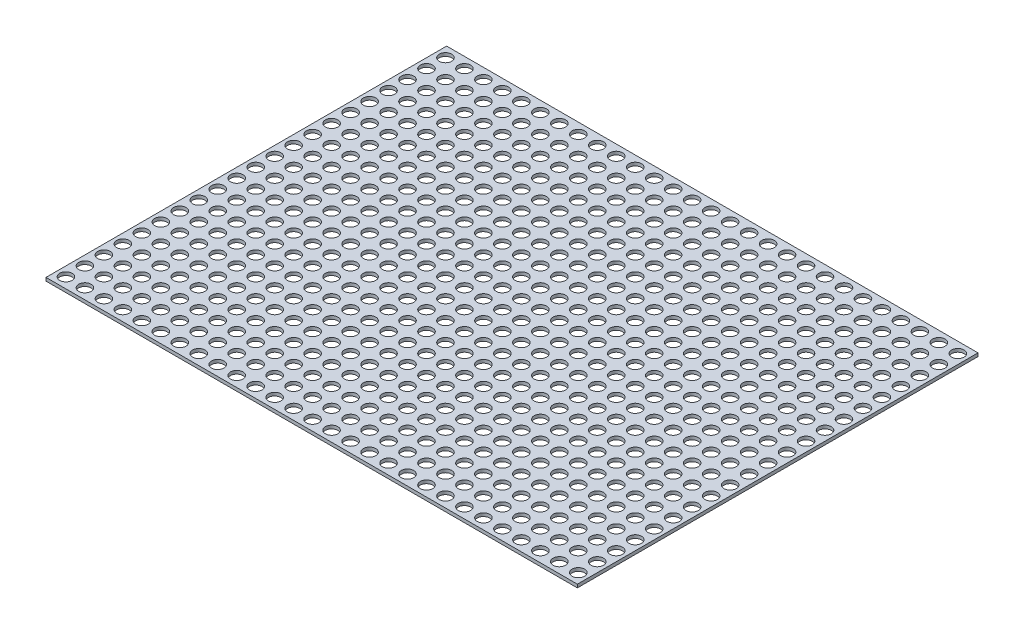
SolidWorks part; units mm, degrees
ref_plane "Front Plane" through (0, 0, 0) normal (0, 0, 1) x (1, 0, 0)
ref_plane "Top Plane" through (0, 0, 0) normal (0, 1, 0) x (1, 0, 0)
ref_plane "Right Plane" through (0, 0, 0) normal (1, 0, 0) x (0, 0, -1)
sketch "Sketch1" plane through (0, 0, 0) normal (0, 1, 0) x (1, 0, 0)
  line L0 (4.5, 4.95) -> (13.5, 4.95) construction
  line L1 (0, 0) -> (252, 0)
  line L2 (0, 0) -> (0, 190)
  line L3 (0, 190) -> (252, 190)
  line L4 (252, 0) -> (252, 190)
  line L5 (4.5, 4.95) -> (4.5, 13.95) construction
  circle A0 centre (4.5, 4.95) radius 2.95
  circle A1 centre (13.5, 4.95) radius 2.95
  circle A2 centre (22.5, 4.95) radius 2.95
  circle A3 centre (31.5, 4.95) radius 2.95
  circle A4 centre (40.5, 4.95) radius 2.95
  circle A5 centre (49.5, 4.95) radius 2.95
  circle A6 centre (58.5, 4.95) radius 2.95
  circle A7 centre (67.5, 4.95) radius 2.95
  circle A8 centre (76.5, 4.95) radius 2.95
  circle A9 centre (85.5, 4.95) radius 2.95
  circle A10 centre (94.5, 4.95) radius 2.95
  circle A11 centre (103.5, 4.95) radius 2.95
  circle A12 centre (112.5, 4.95) radius 2.95
  circle A13 centre (121.5, 4.95) radius 2.95
  circle A14 centre (130.5, 4.95) radius 2.95
  circle A15 centre (139.5, 4.95) radius 2.95
  circle A16 centre (148.5, 4.95) radius 2.95
  circle A17 centre (157.5, 4.95) radius 2.95
  circle A18 centre (166.5, 4.95) radius 2.95
  circle A19 centre (175.5, 4.95) radius 2.95
  circle A20 centre (184.5, 4.95) radius 2.95
  circle A21 centre (193.5, 4.95) radius 2.95
  circle A22 centre (202.5, 4.95) radius 2.95
  circle A23 centre (211.5, 4.95) radius 2.95
  circle A24 centre (220.5, 4.95) radius 2.95
  circle A25 centre (229.5, 4.95) radius 2.95
  circle A26 centre (238.5, 4.95) radius 2.95
  circle A27 centre (247.5, 4.95) radius 2.95
  circle A28 centre (13.5, 13.95) radius 2.95
  circle A29 centre (22.5, 13.95) radius 2.95
  circle A30 centre (31.5, 13.95) radius 2.95
  circle A31 centre (40.5, 13.95) radius 2.95
  circle A32 centre (49.5, 13.95) radius 2.95
  circle A33 centre (58.5, 13.95) radius 2.95
  circle A34 centre (67.5, 13.95) radius 2.95
  circle A35 centre (76.5, 13.95) radius 2.95
  circle A36 centre (85.5, 13.95) radius 2.95
  circle A37 centre (94.5, 13.95) radius 2.95
  circle A38 centre (103.5, 13.95) radius 2.95
  circle A39 centre (112.5, 13.95) radius 2.95
  circle A40 centre (121.5, 13.95) radius 2.95
  circle A41 centre (130.5, 13.95) radius 2.95
  circle A42 centre (139.5, 13.95) radius 2.95
  circle A43 centre (148.5, 13.95) radius 2.95
  circle A44 centre (157.5, 13.95) radius 2.95
  circle A45 centre (166.5, 13.95) radius 2.95
  circle A46 centre (175.5, 13.95) radius 2.95
  circle A47 centre (184.5, 13.95) radius 2.95
  circle A48 centre (193.5, 13.95) radius 2.95
  circle A49 centre (202.5, 13.95) radius 2.95
  circle A50 centre (211.5, 13.95) radius 2.95
  circle A51 centre (220.5, 13.95) radius 2.95
  circle A52 centre (229.5, 13.95) radius 2.95
  circle A53 centre (238.5, 13.95) radius 2.95
  circle A54 centre (247.5, 13.95) radius 2.95
  circle A55 centre (13.5, 22.95) radius 2.95
  circle A56 centre (22.5, 22.95) radius 2.95
  circle A57 centre (31.5, 22.95) radius 2.95
  circle A58 centre (40.5, 22.95) radius 2.95
  circle A59 centre (49.5, 22.95) radius 2.95
  circle A60 centre (58.5, 22.95) radius 2.95
  circle A61 centre (67.5, 22.95) radius 2.95
  circle A62 centre (76.5, 22.95) radius 2.95
  circle A63 centre (85.5, 22.95) radius 2.95
  circle A64 centre (94.5, 22.95) radius 2.95
  circle A65 centre (103.5, 22.95) radius 2.95
  circle A66 centre (112.5, 22.95) radius 2.95
  circle A67 centre (121.5, 22.95) radius 2.95
  circle A68 centre (130.5, 22.95) radius 2.95
  circle A69 centre (139.5, 22.95) radius 2.95
  circle A70 centre (148.5, 22.95) radius 2.95
  circle A71 centre (157.5, 22.95) radius 2.95
  circle A72 centre (166.5, 22.95) radius 2.95
  circle A73 centre (175.5, 22.95) radius 2.95
  circle A74 centre (184.5, 22.95) radius 2.95
  circle A75 centre (193.5, 22.95) radius 2.95
  circle A76 centre (202.5, 22.95) radius 2.95
  circle A77 centre (211.5, 22.95) radius 2.95
  circle A78 centre (220.5, 22.95) radius 2.95
  circle A79 centre (229.5, 22.95) radius 2.95
  circle A80 centre (238.5, 22.95) radius 2.95
  circle A81 centre (247.5, 22.95) radius 2.95
  circle A82 centre (13.5, 31.95) radius 2.95
  circle A83 centre (22.5, 31.95) radius 2.95
  circle A84 centre (31.5, 31.95) radius 2.95
  circle A85 centre (40.5, 31.95) radius 2.95
  circle A86 centre (49.5, 31.95) radius 2.95
  circle A87 centre (58.5, 31.95) radius 2.95
  circle A88 centre (67.5, 31.95) radius 2.95
  circle A89 centre (76.5, 31.95) radius 2.95
  circle A90 centre (85.5, 31.95) radius 2.95
  circle A91 centre (94.5, 31.95) radius 2.95
  circle A92 centre (103.5, 31.95) radius 2.95
  circle A93 centre (112.5, 31.95) radius 2.95
  circle A94 centre (121.5, 31.95) radius 2.95
  circle A95 centre (130.5, 31.95) radius 2.95
  circle A96 centre (139.5, 31.95) radius 2.95
  circle A97 centre (148.5, 31.95) radius 2.95
  circle A98 centre (157.5, 31.95) radius 2.95
  circle A99 centre (166.5, 31.95) radius 2.95
  circle A100 centre (175.5, 31.95) radius 2.95
  circle A101 centre (184.5, 31.95) radius 2.95
  circle A102 centre (193.5, 31.95) radius 2.95
  circle A103 centre (202.5, 31.95) radius 2.95
  circle A104 centre (211.5, 31.95) radius 2.95
  circle A105 centre (220.5, 31.95) radius 2.95
  circle A106 centre (229.5, 31.95) radius 2.95
  circle A107 centre (238.5, 31.95) radius 2.95
  circle A108 centre (247.5, 31.95) radius 2.95
  circle A109 centre (13.5, 40.95) radius 2.95
  circle A110 centre (22.5, 40.95) radius 2.95
  circle A111 centre (31.5, 40.95) radius 2.95
  circle A112 centre (40.5, 40.95) radius 2.95
  circle A113 centre (49.5, 40.95) radius 2.95
  circle A114 centre (58.5, 40.95) radius 2.95
  circle A115 centre (67.5, 40.95) radius 2.95
  circle A116 centre (76.5, 40.95) radius 2.95
  circle A117 centre (85.5, 40.95) radius 2.95
  circle A118 centre (94.5, 40.95) radius 2.95
  circle A119 centre (103.5, 40.95) radius 2.95
  circle A120 centre (112.5, 40.95) radius 2.95
  circle A121 centre (121.5, 40.95) radius 2.95
  circle A122 centre (130.5, 40.95) radius 2.95
  circle A123 centre (139.5, 40.95) radius 2.95
  circle A124 centre (148.5, 40.95) radius 2.95
  circle A125 centre (157.5, 40.95) radius 2.95
  circle A126 centre (166.5, 40.95) radius 2.95
  circle A127 centre (175.5, 40.95) radius 2.95
  circle A128 centre (184.5, 40.95) radius 2.95
  circle A129 centre (193.5, 40.95) radius 2.95
  circle A130 centre (202.5, 40.95) radius 2.95
  circle A131 centre (211.5, 40.95) radius 2.95
  circle A132 centre (220.5, 40.95) radius 2.95
  circle A133 centre (229.5, 40.95) radius 2.95
  circle A134 centre (238.5, 40.95) radius 2.95
  circle A135 centre (247.5, 40.95) radius 2.95
  circle A136 centre (13.5, 49.95) radius 2.95
  circle A137 centre (22.5, 49.95) radius 2.95
  circle A138 centre (31.5, 49.95) radius 2.95
  circle A139 centre (40.5, 49.95) radius 2.95
  circle A140 centre (49.5, 49.95) radius 2.95
  circle A141 centre (58.5, 49.95) radius 2.95
  circle A142 centre (67.5, 49.95) radius 2.95
  circle A143 centre (76.5, 49.95) radius 2.95
  circle A144 centre (85.5, 49.95) radius 2.95
  circle A145 centre (94.5, 49.95) radius 2.95
  circle A146 centre (103.5, 49.95) radius 2.95
  circle A147 centre (112.5, 49.95) radius 2.95
  circle A148 centre (121.5, 49.95) radius 2.95
  circle A149 centre (130.5, 49.95) radius 2.95
  circle A150 centre (139.5, 49.95) radius 2.95
  circle A151 centre (148.5, 49.95) radius 2.95
  circle A152 centre (157.5, 49.95) radius 2.95
  circle A153 centre (166.5, 49.95) radius 2.95
  circle A154 centre (175.5, 49.95) radius 2.95
  circle A155 centre (184.5, 49.95) radius 2.95
  circle A156 centre (193.5, 49.95) radius 2.95
  circle A157 centre (202.5, 49.95) radius 2.95
  circle A158 centre (211.5, 49.95) radius 2.95
  circle A159 centre (220.5, 49.95) radius 2.95
  circle A160 centre (229.5, 49.95) radius 2.95
  circle A161 centre (238.5, 49.95) radius 2.95
  circle A162 centre (247.5, 49.95) radius 2.95
  circle A163 centre (13.5, 58.95) radius 2.95
  circle A164 centre (22.5, 58.95) radius 2.95
  circle A165 centre (31.5, 58.95) radius 2.95
  circle A166 centre (40.5, 58.95) radius 2.95
  circle A167 centre (49.5, 58.95) radius 2.95
  circle A168 centre (58.5, 58.95) radius 2.95
  circle A169 centre (67.5, 58.95) radius 2.95
  circle A170 centre (76.5, 58.95) radius 2.95
  circle A171 centre (85.5, 58.95) radius 2.95
  circle A172 centre (94.5, 58.95) radius 2.95
  circle A173 centre (103.5, 58.95) radius 2.95
  circle A174 centre (112.5, 58.95) radius 2.95
  circle A175 centre (121.5, 58.95) radius 2.95
  circle A176 centre (130.5, 58.95) radius 2.95
  circle A177 centre (139.5, 58.95) radius 2.95
  circle A178 centre (148.5, 58.95) radius 2.95
  circle A179 centre (157.5, 58.95) radius 2.95
  circle A180 centre (166.5, 58.95) radius 2.95
  circle A181 centre (175.5, 58.95) radius 2.95
  circle A182 centre (184.5, 58.95) radius 2.95
  circle A183 centre (193.5, 58.95) radius 2.95
  circle A184 centre (202.5, 58.95) radius 2.95
  circle A185 centre (211.5, 58.95) radius 2.95
  circle A186 centre (220.5, 58.95) radius 2.95
  circle A187 centre (229.5, 58.95) radius 2.95
  circle A188 centre (238.5, 58.95) radius 2.95
  circle A189 centre (247.5, 58.95) radius 2.95
  circle A190 centre (13.5, 67.95) radius 2.95
  circle A191 centre (22.5, 67.95) radius 2.95
  circle A192 centre (31.5, 67.95) radius 2.95
  circle A193 centre (40.5, 67.95) radius 2.95
  circle A194 centre (49.5, 67.95) radius 2.95
  circle A195 centre (58.5, 67.95) radius 2.95
  circle A196 centre (67.5, 67.95) radius 2.95
  circle A197 centre (76.5, 67.95) radius 2.95
  circle A198 centre (85.5, 67.95) radius 2.95
  circle A199 centre (94.5, 67.95) radius 2.95
  circle A200 centre (103.5, 67.95) radius 2.95
  circle A201 centre (112.5, 67.95) radius 2.95
  circle A202 centre (121.5, 67.95) radius 2.95
  circle A203 centre (130.5, 67.95) radius 2.95
  circle A204 centre (139.5, 67.95) radius 2.95
  circle A205 centre (148.5, 67.95) radius 2.95
  circle A206 centre (157.5, 67.95) radius 2.95
  circle A207 centre (166.5, 67.95) radius 2.95
  circle A208 centre (175.5, 67.95) radius 2.95
  circle A209 centre (184.5, 67.95) radius 2.95
  circle A210 centre (193.5, 67.95) radius 2.95
  circle A211 centre (202.5, 67.95) radius 2.95
  circle A212 centre (211.5, 67.95) radius 2.95
  circle A213 centre (220.5, 67.95) radius 2.95
  circle A214 centre (229.5, 67.95) radius 2.95
  circle A215 centre (238.5, 67.95) radius 2.95
  circle A216 centre (247.5, 67.95) radius 2.95
  circle A217 centre (13.5, 76.95) radius 2.95
  circle A218 centre (22.5, 76.95) radius 2.95
  circle A219 centre (31.5, 76.95) radius 2.95
  circle A220 centre (40.5, 76.95) radius 2.95
  circle A221 centre (49.5, 76.95) radius 2.95
  circle A222 centre (58.5, 76.95) radius 2.95
  circle A223 centre (67.5, 76.95) radius 2.95
  circle A224 centre (76.5, 76.95) radius 2.95
  circle A225 centre (85.5, 76.95) radius 2.95
  circle A226 centre (94.5, 76.95) radius 2.95
  circle A227 centre (103.5, 76.95) radius 2.95
  circle A228 centre (112.5, 76.95) radius 2.95
  circle A229 centre (121.5, 76.95) radius 2.95
  circle A230 centre (130.5, 76.95) radius 2.95
  circle A231 centre (139.5, 76.95) radius 2.95
  circle A232 centre (148.5, 76.95) radius 2.95
  circle A233 centre (157.5, 76.95) radius 2.95
  circle A234 centre (166.5, 76.95) radius 2.95
  circle A235 centre (175.5, 76.95) radius 2.95
  circle A236 centre (184.5, 76.95) radius 2.95
  circle A237 centre (193.5, 76.95) radius 2.95
  circle A238 centre (202.5, 76.95) radius 2.95
  circle A239 centre (211.5, 76.95) radius 2.95
  circle A240 centre (220.5, 76.95) radius 2.95
  circle A241 centre (229.5, 76.95) radius 2.95
  circle A242 centre (238.5, 76.95) radius 2.95
  circle A243 centre (247.5, 76.95) radius 2.95
  circle A244 centre (13.5, 85.95) radius 2.95
  circle A245 centre (22.5, 85.95) radius 2.95
  circle A246 centre (31.5, 85.95) radius 2.95
  circle A247 centre (40.5, 85.95) radius 2.95
  circle A248 centre (49.5, 85.95) radius 2.95
  circle A249 centre (58.5, 85.95) radius 2.95
  circle A250 centre (67.5, 85.95) radius 2.95
  circle A251 centre (76.5, 85.95) radius 2.95
  circle A252 centre (85.5, 85.95) radius 2.95
  circle A253 centre (94.5, 85.95) radius 2.95
  circle A254 centre (103.5, 85.95) radius 2.95
  circle A255 centre (112.5, 85.95) radius 2.95
  circle A256 centre (121.5, 85.95) radius 2.95
  circle A257 centre (130.5, 85.95) radius 2.95
  circle A258 centre (139.5, 85.95) radius 2.95
  circle A259 centre (148.5, 85.95) radius 2.95
  circle A260 centre (157.5, 85.95) radius 2.95
  circle A261 centre (166.5, 85.95) radius 2.95
  circle A262 centre (175.5, 85.95) radius 2.95
  circle A263 centre (184.5, 85.95) radius 2.95
  circle A264 centre (193.5, 85.95) radius 2.95
  circle A265 centre (202.5, 85.95) radius 2.95
  circle A266 centre (211.5, 85.95) radius 2.95
  circle A267 centre (220.5, 85.95) radius 2.95
  circle A268 centre (229.5, 85.95) radius 2.95
  circle A269 centre (238.5, 85.95) radius 2.95
  circle A270 centre (247.5, 85.95) radius 2.95
  circle A271 centre (13.5, 94.95) radius 2.95
  circle A272 centre (22.5, 94.95) radius 2.95
  circle A273 centre (31.5, 94.95) radius 2.95
  circle A274 centre (40.5, 94.95) radius 2.95
  circle A275 centre (49.5, 94.95) radius 2.95
  circle A276 centre (58.5, 94.95) radius 2.95
  circle A277 centre (67.5, 94.95) radius 2.95
  circle A278 centre (76.5, 94.95) radius 2.95
  circle A279 centre (85.5, 94.95) radius 2.95
  circle A280 centre (94.5, 94.95) radius 2.95
  circle A281 centre (103.5, 94.95) radius 2.95
  circle A282 centre (112.5, 94.95) radius 2.95
  circle A283 centre (121.5, 94.95) radius 2.95
  circle A284 centre (130.5, 94.95) radius 2.95
  circle A285 centre (139.5, 94.95) radius 2.95
  circle A286 centre (148.5, 94.95) radius 2.95
  circle A287 centre (157.5, 94.95) radius 2.95
  circle A288 centre (166.5, 94.95) radius 2.95
  circle A289 centre (175.5, 94.95) radius 2.95
  circle A290 centre (184.5, 94.95) radius 2.95
  circle A291 centre (193.5, 94.95) radius 2.95
  circle A292 centre (202.5, 94.95) radius 2.95
  circle A293 centre (211.5, 94.95) radius 2.95
  circle A294 centre (220.5, 94.95) radius 2.95
  circle A295 centre (229.5, 94.95) radius 2.95
  circle A296 centre (238.5, 94.95) radius 2.95
  circle A297 centre (247.5, 94.95) radius 2.95
  circle A298 centre (13.5, 103.95) radius 2.95
  circle A299 centre (22.5, 103.95) radius 2.95
  circle A300 centre (31.5, 103.95) radius 2.95
  circle A301 centre (40.5, 103.95) radius 2.95
  circle A302 centre (49.5, 103.95) radius 2.95
  circle A303 centre (58.5, 103.95) radius 2.95
  circle A304 centre (67.5, 103.95) radius 2.95
  circle A305 centre (76.5, 103.95) radius 2.95
  circle A306 centre (85.5, 103.95) radius 2.95
  circle A307 centre (94.5, 103.95) radius 2.95
  circle A308 centre (103.5, 103.95) radius 2.95
  circle A309 centre (112.5, 103.95) radius 2.95
  circle A310 centre (121.5, 103.95) radius 2.95
  circle A311 centre (130.5, 103.95) radius 2.95
  circle A312 centre (139.5, 103.95) radius 2.95
  circle A313 centre (148.5, 103.95) radius 2.95
  circle A314 centre (157.5, 103.95) radius 2.95
  circle A315 centre (166.5, 103.95) radius 2.95
  circle A316 centre (175.5, 103.95) radius 2.95
  circle A317 centre (184.5, 103.95) radius 2.95
  circle A318 centre (193.5, 103.95) radius 2.95
  circle A319 centre (202.5, 103.95) radius 2.95
  circle A320 centre (211.5, 103.95) radius 2.95
  circle A321 centre (220.5, 103.95) radius 2.95
  circle A322 centre (229.5, 103.95) radius 2.95
  circle A323 centre (238.5, 103.95) radius 2.95
  circle A324 centre (247.5, 103.95) radius 2.95
  circle A325 centre (13.5, 112.95) radius 2.95
  circle A326 centre (22.5, 112.95) radius 2.95
  circle A327 centre (31.5, 112.95) radius 2.95
  circle A328 centre (40.5, 112.95) radius 2.95
  circle A329 centre (49.5, 112.95) radius 2.95
  circle A330 centre (58.5, 112.95) radius 2.95
  circle A331 centre (67.5, 112.95) radius 2.95
  circle A332 centre (76.5, 112.95) radius 2.95
  circle A333 centre (85.5, 112.95) radius 2.95
  circle A334 centre (94.5, 112.95) radius 2.95
  circle A335 centre (103.5, 112.95) radius 2.95
  circle A336 centre (112.5, 112.95) radius 2.95
  circle A337 centre (121.5, 112.95) radius 2.95
  circle A338 centre (130.5, 112.95) radius 2.95
  circle A339 centre (139.5, 112.95) radius 2.95
  circle A340 centre (148.5, 112.95) radius 2.95
  circle A341 centre (157.5, 112.95) radius 2.95
  circle A342 centre (166.5, 112.95) radius 2.95
  circle A343 centre (175.5, 112.95) radius 2.95
  circle A344 centre (184.5, 112.95) radius 2.95
  circle A345 centre (193.5, 112.95) radius 2.95
  circle A346 centre (202.5, 112.95) radius 2.95
  circle A347 centre (211.5, 112.95) radius 2.95
  circle A348 centre (220.5, 112.95) radius 2.95
  circle A349 centre (229.5, 112.95) radius 2.95
  circle A350 centre (238.5, 112.95) radius 2.95
  circle A351 centre (247.5, 112.95) radius 2.95
  circle A352 centre (13.5, 121.95) radius 2.95
  circle A353 centre (22.5, 121.95) radius 2.95
  circle A354 centre (31.5, 121.95) radius 2.95
  circle A355 centre (40.5, 121.95) radius 2.95
  circle A356 centre (49.5, 121.95) radius 2.95
  circle A357 centre (58.5, 121.95) radius 2.95
  circle A358 centre (67.5, 121.95) radius 2.95
  circle A359 centre (76.5, 121.95) radius 2.95
  circle A360 centre (85.5, 121.95) radius 2.95
  circle A361 centre (94.5, 121.95) radius 2.95
  circle A362 centre (103.5, 121.95) radius 2.95
  circle A363 centre (112.5, 121.95) radius 2.95
  circle A364 centre (121.5, 121.95) radius 2.95
  circle A365 centre (130.5, 121.95) radius 2.95
  circle A366 centre (139.5, 121.95) radius 2.95
  circle A367 centre (148.5, 121.95) radius 2.95
  circle A368 centre (157.5, 121.95) radius 2.95
  circle A369 centre (166.5, 121.95) radius 2.95
  circle A370 centre (175.5, 121.95) radius 2.95
  circle A371 centre (184.5, 121.95) radius 2.95
  circle A372 centre (193.5, 121.95) radius 2.95
  circle A373 centre (202.5, 121.95) radius 2.95
  circle A374 centre (211.5, 121.95) radius 2.95
  circle A375 centre (220.5, 121.95) radius 2.95
  circle A376 centre (229.5, 121.95) radius 2.95
  circle A377 centre (238.5, 121.95) radius 2.95
  circle A378 centre (247.5, 121.95) radius 2.95
  circle A379 centre (13.5, 130.95) radius 2.95
  circle A380 centre (22.5, 130.95) radius 2.95
  circle A381 centre (31.5, 130.95) radius 2.95
  circle A382 centre (40.5, 130.95) radius 2.95
  circle A383 centre (49.5, 130.95) radius 2.95
  circle A384 centre (58.5, 130.95) radius 2.95
  circle A385 centre (67.5, 130.95) radius 2.95
  circle A386 centre (76.5, 130.95) radius 2.95
  circle A387 centre (85.5, 130.95) radius 2.95
  circle A388 centre (94.5, 130.95) radius 2.95
  circle A389 centre (103.5, 130.95) radius 2.95
  circle A390 centre (112.5, 130.95) radius 2.95
  circle A391 centre (121.5, 130.95) radius 2.95
  circle A392 centre (130.5, 130.95) radius 2.95
  circle A393 centre (139.5, 130.95) radius 2.95
  circle A394 centre (148.5, 130.95) radius 2.95
  circle A395 centre (157.5, 130.95) radius 2.95
  circle A396 centre (166.5, 130.95) radius 2.95
  circle A397 centre (175.5, 130.95) radius 2.95
  circle A398 centre (184.5, 130.95) radius 2.95
  circle A399 centre (193.5, 130.95) radius 2.95
  circle A400 centre (202.5, 130.95) radius 2.95
  circle A401 centre (211.5, 130.95) radius 2.95
  circle A402 centre (220.5, 130.95) radius 2.95
  circle A403 centre (229.5, 130.95) radius 2.95
  circle A404 centre (238.5, 130.95) radius 2.95
  circle A405 centre (247.5, 130.95) radius 2.95
  circle A406 centre (13.5, 139.95) radius 2.95
  circle A407 centre (22.5, 139.95) radius 2.95
  circle A408 centre (31.5, 139.95) radius 2.95
  circle A409 centre (40.5, 139.95) radius 2.95
  circle A410 centre (49.5, 139.95) radius 2.95
  circle A411 centre (58.5, 139.95) radius 2.95
  circle A412 centre (67.5, 139.95) radius 2.95
  circle A413 centre (76.5, 139.95) radius 2.95
  circle A414 centre (85.5, 139.95) radius 2.95
  circle A415 centre (94.5, 139.95) radius 2.95
  circle A416 centre (103.5, 139.95) radius 2.95
  circle A417 centre (112.5, 139.95) radius 2.95
  circle A418 centre (121.5, 139.95) radius 2.95
  circle A419 centre (130.5, 139.95) radius 2.95
  circle A420 centre (139.5, 139.95) radius 2.95
  circle A421 centre (148.5, 139.95) radius 2.95
  circle A422 centre (157.5, 139.95) radius 2.95
  circle A423 centre (166.5, 139.95) radius 2.95
  circle A424 centre (175.5, 139.95) radius 2.95
  circle A425 centre (184.5, 139.95) radius 2.95
  circle A426 centre (193.5, 139.95) radius 2.95
  circle A427 centre (202.5, 139.95) radius 2.95
  circle A428 centre (211.5, 139.95) radius 2.95
  circle A429 centre (220.5, 139.95) radius 2.95
  circle A430 centre (229.5, 139.95) radius 2.95
  circle A431 centre (238.5, 139.95) radius 2.95
  circle A432 centre (247.5, 139.95) radius 2.95
  circle A433 centre (13.5, 148.95) radius 2.95
  circle A434 centre (22.5, 148.95) radius 2.95
  circle A435 centre (31.5, 148.95) radius 2.95
  circle A436 centre (40.5, 148.95) radius 2.95
  circle A437 centre (49.5, 148.95) radius 2.95
  circle A438 centre (58.5, 148.95) radius 2.95
  circle A439 centre (67.5, 148.95) radius 2.95
  circle A440 centre (76.5, 148.95) radius 2.95
  circle A441 centre (85.5, 148.95) radius 2.95
  circle A442 centre (94.5, 148.95) radius 2.95
  circle A443 centre (103.5, 148.95) radius 2.95
  circle A444 centre (112.5, 148.95) radius 2.95
  circle A445 centre (121.5, 148.95) radius 2.95
  circle A446 centre (130.5, 148.95) radius 2.95
  circle A447 centre (139.5, 148.95) radius 2.95
  circle A448 centre (148.5, 148.95) radius 2.95
  circle A449 centre (157.5, 148.95) radius 2.95
  circle A450 centre (166.5, 148.95) radius 2.95
  circle A451 centre (175.5, 148.95) radius 2.95
  circle A452 centre (184.5, 148.95) radius 2.95
  circle A453 centre (193.5, 148.95) radius 2.95
  circle A454 centre (202.5, 148.95) radius 2.95
  circle A455 centre (211.5, 148.95) radius 2.95
  circle A456 centre (220.5, 148.95) radius 2.95
  circle A457 centre (229.5, 148.95) radius 2.95
  circle A458 centre (238.5, 148.95) radius 2.95
  circle A459 centre (247.5, 148.95) radius 2.95
  circle A460 centre (13.5, 157.95) radius 2.95
  circle A461 centre (22.5, 157.95) radius 2.95
  circle A462 centre (31.5, 157.95) radius 2.95
  circle A463 centre (40.5, 157.95) radius 2.95
  circle A464 centre (49.5, 157.95) radius 2.95
  circle A465 centre (58.5, 157.95) radius 2.95
  circle A466 centre (67.5, 157.95) radius 2.95
  circle A467 centre (76.5, 157.95) radius 2.95
  circle A468 centre (85.5, 157.95) radius 2.95
  circle A469 centre (94.5, 157.95) radius 2.95
  circle A470 centre (103.5, 157.95) radius 2.95
  circle A471 centre (112.5, 157.95) radius 2.95
  circle A472 centre (121.5, 157.95) radius 2.95
  circle A473 centre (130.5, 157.95) radius 2.95
  circle A474 centre (139.5, 157.95) radius 2.95
  circle A475 centre (148.5, 157.95) radius 2.95
  circle A476 centre (157.5, 157.95) radius 2.95
  circle A477 centre (166.5, 157.95) radius 2.95
  circle A478 centre (175.5, 157.95) radius 2.95
  circle A479 centre (184.5, 157.95) radius 2.95
  circle A480 centre (193.5, 157.95) radius 2.95
  circle A481 centre (202.5, 157.95) radius 2.95
  circle A482 centre (211.5, 157.95) radius 2.95
  circle A483 centre (220.5, 157.95) radius 2.95
  circle A484 centre (229.5, 157.95) radius 2.95
  circle A485 centre (238.5, 157.95) radius 2.95
  circle A486 centre (247.5, 157.95) radius 2.95
  circle A487 centre (13.5, 166.95) radius 2.95
  circle A488 centre (22.5, 166.95) radius 2.95
  circle A489 centre (31.5, 166.95) radius 2.95
  circle A490 centre (40.5, 166.95) radius 2.95
  circle A491 centre (49.5, 166.95) radius 2.95
  circle A492 centre (58.5, 166.95) radius 2.95
  circle A493 centre (67.5, 166.95) radius 2.95
  circle A494 centre (76.5, 166.95) radius 2.95
  circle A495 centre (85.5, 166.95) radius 2.95
  circle A496 centre (94.5, 166.95) radius 2.95
  circle A497 centre (103.5, 166.95) radius 2.95
  circle A498 centre (112.5, 166.95) radius 2.95
  circle A499 centre (121.5, 166.95) radius 2.95
  circle A500 centre (130.5, 166.95) radius 2.95
  circle A501 centre (139.5, 166.95) radius 2.95
  circle A502 centre (148.5, 166.95) radius 2.95
  circle A503 centre (157.5, 166.95) radius 2.95
  circle A504 centre (166.5, 166.95) radius 2.95
  circle A505 centre (175.5, 166.95) radius 2.95
  circle A506 centre (184.5, 166.95) radius 2.95
  circle A507 centre (193.5, 166.95) radius 2.95
  circle A508 centre (202.5, 166.95) radius 2.95
  circle A509 centre (211.5, 166.95) radius 2.95
  circle A510 centre (220.5, 166.95) radius 2.95
  circle A511 centre (229.5, 166.95) radius 2.95
  circle A512 centre (238.5, 166.95) radius 2.95
  circle A513 centre (247.5, 166.95) radius 2.95
  circle A514 centre (13.5, 175.95) radius 2.95
  circle A515 centre (22.5, 175.95) radius 2.95
  circle A516 centre (31.5, 175.95) radius 2.95
  circle A517 centre (40.5, 175.95) radius 2.95
  circle A518 centre (49.5, 175.95) radius 2.95
  circle A519 centre (58.5, 175.95) radius 2.95
  circle A520 centre (67.5, 175.95) radius 2.95
  circle A521 centre (76.5, 175.95) radius 2.95
  circle A522 centre (85.5, 175.95) radius 2.95
  circle A523 centre (94.5, 175.95) radius 2.95
  circle A524 centre (103.5, 175.95) radius 2.95
  circle A525 centre (112.5, 175.95) radius 2.95
  circle A526 centre (121.5, 175.95) radius 2.95
  circle A527 centre (130.5, 175.95) radius 2.95
  circle A528 centre (139.5, 175.95) radius 2.95
  circle A529 centre (148.5, 175.95) radius 2.95
  circle A530 centre (157.5, 175.95) radius 2.95
  circle A531 centre (166.5, 175.95) radius 2.95
  circle A532 centre (175.5, 175.95) radius 2.95
  circle A533 centre (184.5, 175.95) radius 2.95
  circle A534 centre (193.5, 175.95) radius 2.95
  circle A535 centre (202.5, 175.95) radius 2.95
  circle A536 centre (211.5, 175.95) radius 2.95
  circle A537 centre (220.5, 175.95) radius 2.95
  circle A538 centre (229.5, 175.95) radius 2.95
  circle A539 centre (238.5, 175.95) radius 2.95
  circle A540 centre (247.5, 175.95) radius 2.95
  circle A541 centre (13.5, 184.95) radius 2.95
  circle A542 centre (22.5, 184.95) radius 2.95
  circle A543 centre (31.5, 184.95) radius 2.95
  circle A544 centre (40.5, 184.95) radius 2.95
  circle A545 centre (49.5, 184.95) radius 2.95
  circle A546 centre (58.5, 184.95) radius 2.95
  circle A547 centre (67.5, 184.95) radius 2.95
  circle A548 centre (76.5, 184.95) radius 2.95
  circle A549 centre (85.5, 184.95) radius 2.95
  circle A550 centre (94.5, 184.95) radius 2.95
  circle A551 centre (103.5, 184.95) radius 2.95
  circle A552 centre (112.5, 184.95) radius 2.95
  circle A553 centre (121.5, 184.95) radius 2.95
  circle A554 centre (130.5, 184.95) radius 2.95
  circle A555 centre (139.5, 184.95) radius 2.95
  circle A556 centre (148.5, 184.95) radius 2.95
  circle A557 centre (157.5, 184.95) radius 2.95
  circle A558 centre (166.5, 184.95) radius 2.95
  circle A559 centre (175.5, 184.95) radius 2.95
  circle A560 centre (184.5, 184.95) radius 2.95
  circle A561 centre (193.5, 184.95) radius 2.95
  circle A562 centre (202.5, 184.95) radius 2.95
  circle A563 centre (211.5, 184.95) radius 2.95
  circle A564 centre (220.5, 184.95) radius 2.95
  circle A565 centre (229.5, 184.95) radius 2.95
  circle A566 centre (238.5, 184.95) radius 2.95
  circle A567 centre (247.5, 184.95) radius 2.95
  circle A568 centre (4.5, 13.95) radius 2.95
  circle A569 centre (4.5, 22.95) radius 2.95
  circle A570 centre (4.5, 31.95) radius 2.95
  circle A571 centre (4.5, 40.95) radius 2.95
  circle A572 centre (4.5, 49.95) radius 2.95
  circle A573 centre (4.5, 58.95) radius 2.95
  circle A574 centre (4.5, 67.95) radius 2.95
  circle A575 centre (4.5, 76.95) radius 2.95
  circle A576 centre (4.5, 85.95) radius 2.95
  circle A577 centre (4.5, 94.95) radius 2.95
  circle A578 centre (4.5, 103.95) radius 2.95
  circle A579 centre (4.5, 112.95) radius 2.95
  circle A580 centre (4.5, 121.95) radius 2.95
  circle A581 centre (4.5, 130.95) radius 2.95
  circle A582 centre (4.5, 139.95) radius 2.95
  circle A583 centre (4.5, 148.95) radius 2.95
  circle A584 centre (4.5, 157.95) radius 2.95
  circle A585 centre (4.5, 166.95) radius 2.95
  circle A586 centre (4.5, 175.95) radius 2.95
  circle A587 centre (4.5, 184.95) radius 2.95
  dimension "D3" = 5.9
  dimension "D1" = 252
  dimension "D2" = 190
  dimension "D4" = 4.95
  dimension "D5" = 4.5
  dimension "D8" = 9
  dimension "D9" = 9
  dimension "D6" = 28
  dimension "D7" = 21
extrude "Boss-Extrude1" add sketch "Sketch1" along normal blind 1.55 contours L1 L4 L3 L2 A587 A586 A585 A584 A583 A582 A581 A580 A579 A578 A577 A576 A575 A574 A573 A572 A571 A570 A569 A568 A567 A566 A565 region at (126, 0, -95.0253)
equation "\"Length\"= 283mm"
equation "\"Width\"= 225mm"
equation "\"WallThickness\"= 12.5mm"
equation "\"UpperWaterJacketThickness\"= 28mm"
equation "\"SpacerHeight\"= 80.2mm"
equation "\"PlateLength\"= 252mm"
equation "\"D1@Sketch1\"=\"PlateLength\""
equation "\"PlateWidth\"= 190mm"
equation "\"D2@Sketch1\"=\"PlateWidth\""
equation "\"PlateHoleDiameter\"= 5.9mm"
equation "\"D3@Sketch1\"=\"PlateHoleDiameter\""
equation "\"PlateHoleBottom\"= 2mm"
equation "\"D4@Sketch1\"=\"PlateHoleBottom\"+\"PlateHoleDiameter\"/2"
equation "\"PlateHoleSide\"= 1.55mm"
equation "\"D5@Sketch1\"=\"PlateHoleSide\"+\"PlateHoleDiameter\"/2"
equation "\"PlateHoleSpacing\"= 3.1mm"
equation "\"D8@Sketch1\"=\"PlateHoleSpacing\"+\"PlateHoleDiameter\""
equation "\"D9@Sketch1\"=\"PlateHoleSpacing\"+\"PlateHoleDiameter\""
equation "\"PlateThickness\"= 1.55mm"
equation "\"D1@Boss-Extrude1\"=\"PlateThickness\""
